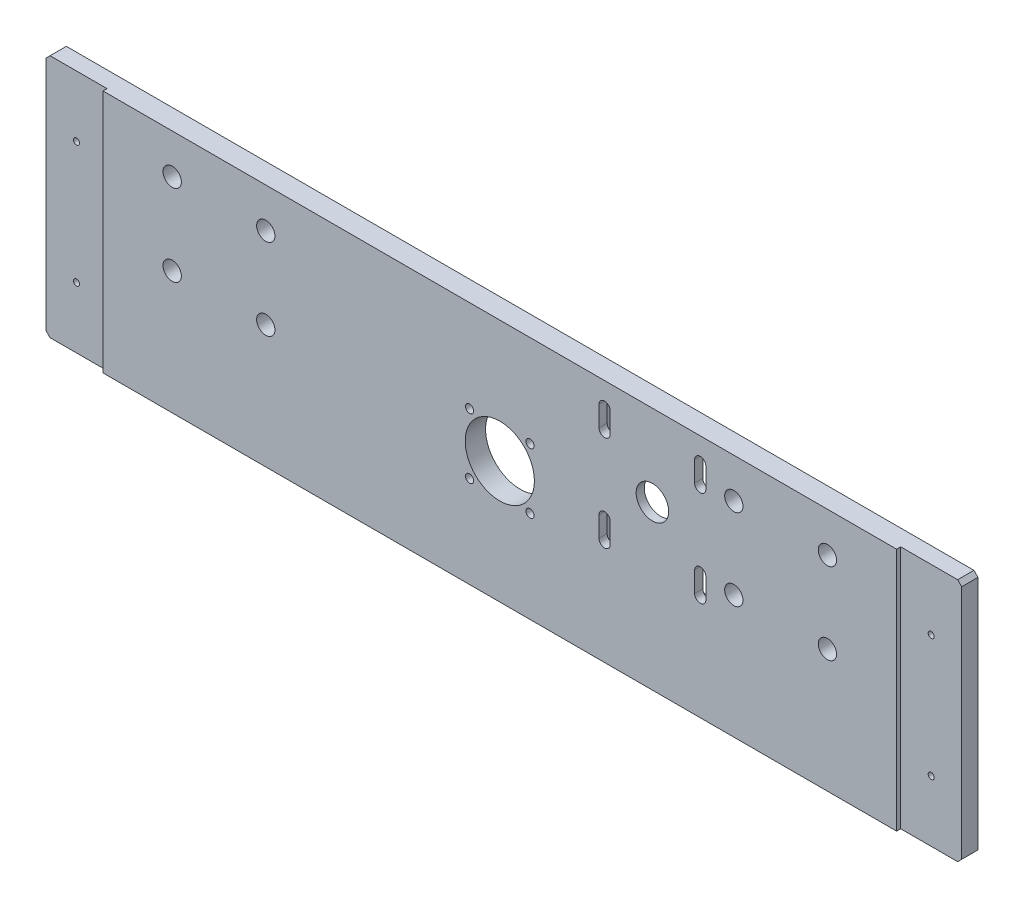
SolidWorks part; units mm, degrees
ref_plane "Piano frontale" through (0, 0, 0) normal (0, 0, 1) x (1, 0, 0)
ref_plane "Piano superiore" through (0, 0, 0) normal (0, 1, 0) x (1, 0, 0)
ref_plane "Piano destro" through (0, 0, 0) normal (1, 0, 0) x (0, 0, -1)
sketch "Schizzo1" plane through (0, 0, 0) normal (0, 0, 1) x (1, 0, 0)
  line L0 (225, 120) -> (225, 0) construction
  line L1 (2, 0) -> (448, 0)
  line L2 (0, 2) -> (0, 118)
  line L3 (2, 120) -> (448, 120)
  line L4 (450, 2) -> (450, 118)
  line L7 (225, 60) -> (243.5099, 60) construction
  line L9 (225, 60) -> (194.6932, 90.3068) construction
  line L21 (0, 118) -> (2, 120)
  line L22 (2, 0) -> (0, 2)
  line L23 (448, 0) -> (450, 2)
  line L24 (448, 120) -> (450, 118)
  line L25 (225, 60) -> (450, 60) construction
  line L26 (344.754, 80) -> (282.8483, 80) construction
  line L27 (323.5, 108.5) -> (323.5, 98.5) construction
  line L28 (320.75, 108.5) -> (320.75, 98.5)
  line L29 (326.25, 108.5) -> (326.25, 98.5)
  line L30 (276.5, 108.5) -> (276.5, 98.5) construction
  line L31 (279.25, 108.5) -> (279.25, 98.5)
  line L32 (273.75, 108.5) -> (273.75, 98.5)
  line L33 (323.5, 51.5) -> (323.5, 61.5) construction
  line L34 (320.75, 51.5) -> (320.75, 61.5)
  line L35 (326.25, 51.5) -> (326.25, 61.5)
  line L36 (276.5, 51.5) -> (276.5, 61.5) construction
  line L37 (279.25, 51.5) -> (279.25, 61.5)
  line L38 (273.75, 51.5) -> (273.75, 61.5)
  line L42 (300, 120) -> (300, 0) construction
  circle A0 centre (225, 60) radius 17
  circle A1 centre (225, 60) radius 21 construction
  circle A2 centre (239.8492, 74.8492) radius 2
  circle A3 centre (386, 100.5) radius 4.5
  circle A4 centre (239.8492, 45.1508) radius 2
  circle A5 centre (210.1508, 45.1508) radius 2
  circle A6 centre (110, 100.5) radius 4.5
  circle A7 centre (110, 60.5) radius 4.5
  circle A8 centre (64, 60.5) radius 4.5
  circle A9 centre (64, 100.5) radius 4.5
  circle A10 centre (386, 60.5) radius 4.5
  circle A11 centre (15, 30) radius 1.5
  circle A12 centre (435, 30) radius 1.5
  circle A13 centre (210.1508, 74.8492) radius 2
  circle A14 centre (340, 60.5) radius 4.5
  circle A15 centre (340, 100.5) radius 4.5
  circle A17 centre (435, 90) radius 1.5
  circle A18 centre (15, 90) radius 1.5
  arc A19 (320.75, 108.5) -> (326.25, 108.5) centre (323.5, 108.5) cw
  arc A20 (326.25, 98.5) -> (320.75, 98.5) centre (323.5, 98.5) cw
  arc A21 (279.25, 108.5) -> (273.75, 108.5) centre (276.5, 108.5) ccw
  arc A22 (273.75, 98.5) -> (279.25, 98.5) centre (276.5, 98.5) ccw
  arc A23 (320.75, 51.5) -> (326.25, 51.5) centre (323.5, 51.5) ccw
  arc A24 (326.25, 61.5) -> (320.75, 61.5) centre (323.5, 61.5) ccw
  arc A25 (279.25, 51.5) -> (273.75, 51.5) centre (276.5, 51.5) cw
  arc A26 (273.75, 61.5) -> (279.25, 61.5) centre (276.5, 61.5) cw
  circle A27 centre (300, 80) radius 8
  point P0 (0, 0)
  point P1 (450, 120)
  point P2 (0, 120)
  point P3 (450, 0)
  point P9 (210.1508, 74.8492)
  point P13 (210.1508, 74.8492)
  point P80 (300, 80)
  point P83 (323.5, 103.5)
  point P90 (276.5, 103.5)
  point P97 (323.5, 56.5)
  point P104 (276.5, 56.5)
  dimension "D4" = 34
  dimension "D15" = 3
  dimension "D17" = 4
  dimension "D25" = 16
  dimension "D8" = 45
  dimension "D5" = 42
  dimension "D1" = 120
  dimension "D2" = 450
  dimension "D3" = 60
  dimension "D14" = 30
  dimension "D16" = 15
  dimension "D18" = 40
  dimension "D23" = 23.5
  dimension "D24" = 23.5
  dimension "D26" = 5.5
  dimension "D27" = 10
  dimension "D29" = 150
extrude "Estrusione-Estrusione1" add sketch "Schizzo1" against normal blind 10
sketch "Schizzo2" plane through (0, 0, 0) normal (0, 0, 1) x (1, 0, 0)
  line L0 (448, 120) -> (2, 120) construction
  line L1 (30, 120) -> (0, 120)
  line L2 (30, 120) -> (30, 0)
  line L3 (30, 0) -> (0, 0)
  line L4 (0, 120) -> (0, 0)
  line L5 (225, 120) -> (225, 0) construction
  line L6 (630.4389, 120) -> (630.4389, 0)
  line L7 (600.4389, 0) -> (630.4389, 0)
  line L8 (600.4389, 120) -> (600.4389, 0)
  line L9 (600.4389, 120) -> (630.4389, 120)
  line L10 (2, 0) -> (448, 0) construction
  line L11 (450, 120) -> (450, 0)
  line L12 (420, 0) -> (450, 0)
  line L13 (420, 120) -> (420, 0)
  line L14 (420, 120) -> (450, 120)
  dimension "D1" = 30
extrude "Taglio-Estrusione1" cut sketch "Schizzo2" against normal blind 2
sketch "Schizzo3" plane through (0, 0, -10) normal (0, 0, -1) x (-1, 0, 0)
  line L0 (-300, 80) -> (-300, 120) construction
  line L2 (-300, 80) -> (-346.4615, 80) construction
  line L4 (-270, 44) -> (-330, 44)
  line L5 (-270, 44) -> (-270, 116)
  line L6 (-270, 116) -> (-330, 116)
  line L7 (-330, 44) -> (-330, 116)
  line L8 (-270, 44) -> (-330, 116) construction
  line L9 (-270, 116) -> (-330, 44) construction
  dimension "D1" = 60
  dimension "D2" = 72
extrude "Taglio-Estrusione2" cut sketch "Schizzo3" against normal blind 6
